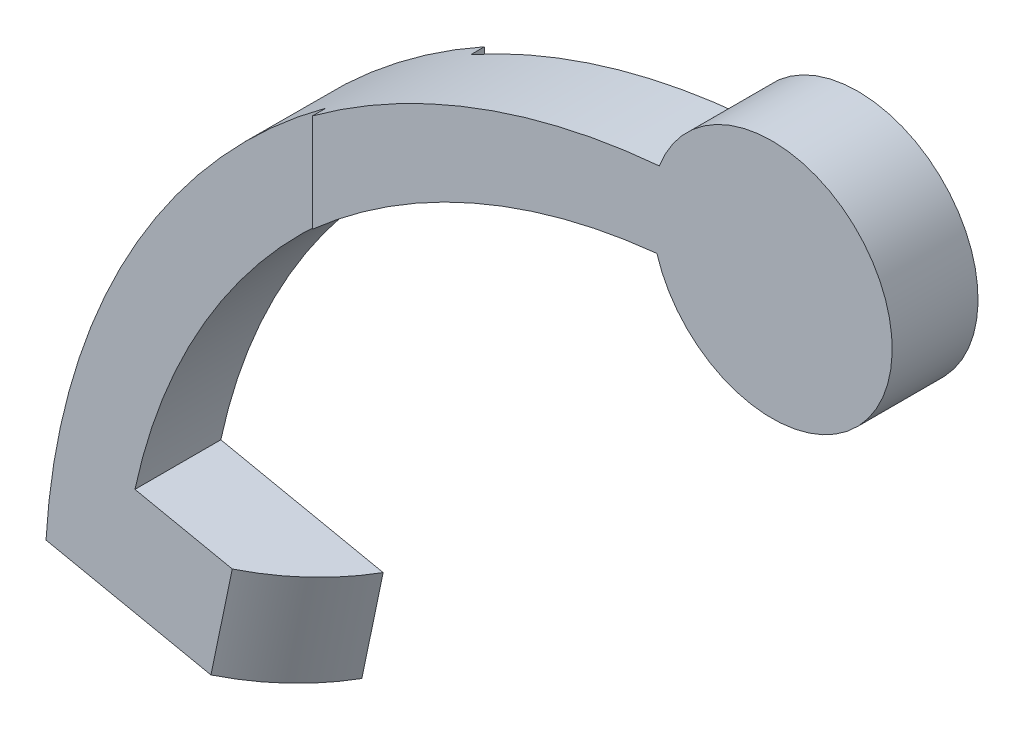
SolidWorks part; units mm, degrees
ref_plane "Front Plane" through (0, 0, 0) normal (0, 0, 1) x (1, 0, 0)
ref_plane "Top Plane" through (0, 0, 0) normal (0, 1, 0) x (1, 0, 0)
ref_plane "Right Plane" through (0, 0, 0) normal (1, 0, 0) x (0, 0, -1)
sketch "Esquisse3" plane through (0, 0, 0) normal (0, 0, 1) x (1, 0, 0)
  line L0 (-43.0597, -35.0596) -> (-29.6704, -37.8465)
  line L1 (-29.6704, -37.8465) -> (-28.4288, -31.8813)
  line L2 (-28.4288, -31.8813) -> (-37.881, -29.9139)
  circle A0 centre (0, 0) radius 7
  arc A1 (-6.5562, 2.4527) -> (-43.0597, -35.0596) centre (-3.1282, -37.4001) ccw
  arc A2 (-37.881, -29.9139) -> (-6.6992, -2.0301) centre (-3.1282, -37.4001) cw
  dimension "D1" = 14
  dimension "D2" = 40
extrude "Boss.-Extru.2" add sketch "Esquisse3" along normal blind 5 contours A0 region at (0, 0, 0)
extrude "Boss.-Extru.3" add sketch "Esquisse3<3>" along normal blind 45 contours L2 A2 A0 A1 L0 L1 region at (-31.4057, -9.8832, 0)
sketch "Esquisse3<3>" plane through (0, 0, 0) normal (0, 0, 1) x (1, 0, 0) same geometry as "Esquisse3"
sketch "Esquisse4" plane through (0, 0, 0) normal (0, 1, 0) x (1, 0, 0)
  line L0 (-6.5562, 0) -> (-6.5562, -5)
  line L4 (-6.5562, -5) -> (-6.5562, 0) construction
  line L6 (-6.5562, -45) -> (-6.5562, -5) construction
  line L8 (-6.5562, -21.6438) -> (-6.5562, -5)
  line L10 (-43.0597, -11.9185) -> (-43.0597, -53.527)
  line L11 (-43.0597, -53.527) -> (-6.4252, -53.527)
  line L12 (-6.4252, -53.527) -> (-6.5562, -21.6438)
  line L13 (-43.0597, -11.9185) -> (-43.0597, -5.792)
  line L14 (-43.0597, -45) -> (-43.0597, 0) construction
  line L15 (-6.5562, 0) -> (-43.0597, 0) construction
  line L16 (-43.0597, -45) -> (-43.0597, 0)
  line L17 (-6.5562, 0) -> (-43.0597, 0)
  line L18 (-26.7522, 0) -> (-26.7522, -0.792)
  line L19 (-26.7522, -0.792) -> (-43.0597, -0.792)
  line L20 (-43.0597, -0.792) -> (-43.0597, -5.792)
  line L21 (-43.0597, -5.792) -> (-22.5349, -5.792)
  line L22 (-22.5349, -5.792) -> (-22.5349, -5)
  line L23 (-22.5349, -5) -> (-6.5562, -5)
  dimension "D2" = 5
extrude "Enlèv. mat.-Extru.3" cut sketch "Esquisse4" against normal through all and the other way blind 5 contours L8 region at (-24.7123, 0, 29.5005)
extrude "Enlèv. mat.-Extru.4" cut sketch "Esquisse4<4>" against normal through all contours L19 L18 L17 L16 region at (-34.906, 0, 0.396)
sketch "Esquisse4<4>" plane through (0, 0, 0) normal (0, 1, 0) x (1, 0, 0) same geometry as "Esquisse4"
sketch "Esquisse5" plane through (-7.5408, -36.229, 0) normal (0.2038, 0.979, 0) x (0.979, -0.2038, 0)
  line L0 (-30.9904, -0.792) -> (-21.3357, -0.792) construction
  line L1 (-25.2022, -0.792) -> (-21.3357, -0.792)
  line L2 (-21.3357, -0.792) -> (-21.3357, -5.792)
  line L5 (-30.9904, -5.792) -> (-21.3357, -5.792) construction
  arc A2 (-21.3357, -5.792) -> (-25.2022, -0.792) centre (-33.4502, -11.1653) ccw
extrude "Enlèv. mat.-Extru.6" cut sketch "Esquisse5" against normal through all
ref_plane "Plan1" through (0, 0, 2.5) normal (0, 0, 1) x (1, 0, 0)
mirror "Symétrie1" about plane through (0, 0, 2.5) normal (0, 0, 1) of "Enlèv. mat.-Extru.3", "Enlèv. mat.-Extru.4", "Boss.-Extru.3", "Enlèv. mat.-Extru.6"
sketch "Esquisse6" plane through (0, 0, 0) normal (0, 1, 0) x (1, 0, 0)
  line L0 (-22.5349, -1196.8249) -> (-22.5349, -5)
  line L2 (-43.0597, -5.792) -> (-22.5349, -5.792) construction
  line L3 (-43.0597, -5.792) -> (-43.0597, -5) construction
  line L4 (-22.5349, -5.792) -> (-22.5349, -5) construction
  line L5 (-28.704, -5.792) -> (-22.5349, -1196.8249)
  line L6 (-43.0597, -5.792) -> (-28.704, -5.792)
  line L7 (-43.0597, -5.792) -> (-43.0597, -5)
  line L9 (-43.0597, -5) -> (-22.5349, -5)
  line L10 (-26.7522, -5) -> (-43.0597, -5) construction
  point P3 (-22.5349, -2.4921)
extrude "Enlèv. mat.-Extru.7" cut sketch "Esquisse6" against normal through all
